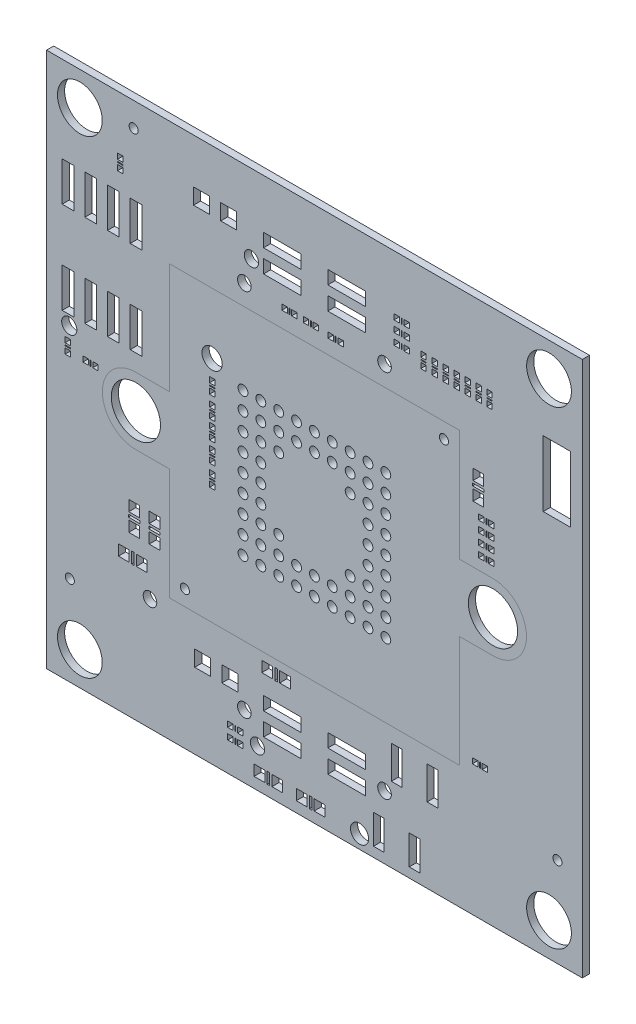
SolidWorks part; units mm, degrees
ref_plane "Front Plane" through (0, 0, 0) normal (0, 0, 1) x (1, 0, 0)
ref_plane "Top Plane" through (0, 0, 0) normal (0, 1, 0) x (1, 0, 0)
ref_plane "Right Plane" through (0, 0, 0) normal (1, 0, 0) x (0, 0, -1)
sketch "Model" plane through (0, 0, 0) normal (0, 0, 1) x (1, 0, 0)
  line L0 (482.6873, 104.7955) -> (482.6873, 151.0459)
  line L1 (482.6873, 151.0459) -> (497.6848, 151.0459)
  line L2 (497.6848, 151.0459) -> (497.6848, 104.7955)
  line L3 (497.6848, 104.7955) -> (482.6873, 104.7955)
  line L4 (532.6873, 104.7955) -> (532.6873, 151.0459)
  line L5 (532.6873, 151.0459) -> (547.6848, 151.0459)
  line L6 (547.6848, 151.0459) -> (547.6848, 104.7955)
  line L7 (547.6848, 104.7955) -> (532.6873, 104.7955)
  line L8 (457.6873, 13.5452) -> (457.6873, 54.7955)
  line L9 (457.6873, 54.7955) -> (472.6848, 54.7955)
  line L10 (472.6848, 54.7955) -> (472.6848, 13.5452)
  line L11 (472.6848, 13.5452) -> (457.6873, 13.5452)
  line L12 (507.6873, 13.5452) -> (507.6873, 54.7955)
  line L13 (507.6873, 54.7955) -> (522.6848, 54.7955)
  line L14 (522.6848, 54.7955) -> (522.6848, 13.5452)
  line L15 (522.6848, 13.5452) -> (507.6873, 13.5452)
  line L16 (356.2506, 69.0119) -> (303.7506, 69.0119)
  line L17 (303.7506, 69.0119) -> (303.7506, 87.7623)
  line L18 (303.7506, 87.7623) -> (356.2506, 87.7623)
  line L19 (356.2506, 87.7623) -> (356.2506, 69.0119)
  line L20 (356.2506, 100.762) -> (303.7506, 100.762)
  line L21 (303.7506, 100.762) -> (303.7506, 119.5123)
  line L22 (303.7506, 119.5123) -> (356.2506, 119.5123)
  line L23 (356.2506, 119.5123) -> (356.2506, 100.762)
  line L24 (446.2506, 69.0119) -> (393.7506, 69.0119)
  line L25 (393.7506, 69.0119) -> (393.7506, 87.7623)
  line L26 (393.7506, 87.7623) -> (446.2506, 87.7623)
  line L27 (446.2506, 87.7623) -> (446.2506, 69.0119)
  line L28 (446.2506, 100.762) -> (393.7506, 100.762)
  line L29 (393.7506, 100.762) -> (393.7506, 119.5123)
  line L30 (393.7506, 119.5123) -> (446.2506, 119.5123)
  line L31 (446.2506, 119.5123) -> (446.2506, 100.762)
  line L32 (356.2506, 630.4877) -> (303.7506, 630.4877)
  line L33 (303.7506, 630.4877) -> (303.7506, 649.238)
  line L34 (303.7506, 649.238) -> (356.2506, 649.238)
  line L35 (356.2506, 649.238) -> (356.2506, 630.4877)
  line L36 (356.2506, 662.2377) -> (303.7506, 662.2377)
  line L37 (303.7506, 662.2377) -> (303.7506, 680.9881)
  line L38 (303.7506, 680.9881) -> (356.2506, 680.9881)
  line L39 (356.2506, 680.9881) -> (356.2506, 662.2377)
  line L40 (446.2506, 630.4877) -> (393.7506, 630.4877)
  line L41 (393.7506, 630.4877) -> (393.7506, 649.238)
  line L42 (393.7506, 649.238) -> (446.2506, 649.238)
  line L43 (446.2506, 649.238) -> (446.2506, 630.4877)
  line L44 (446.2506, 662.2377) -> (393.7506, 662.2377)
  line L45 (393.7506, 662.2377) -> (393.7506, 680.9881)
  line L46 (393.7506, 680.9881) -> (446.2506, 680.9881)
  line L47 (446.2506, 680.9881) -> (446.2506, 662.2377)
  line L48 (603.6868, 190.2972) -> (603.6868, 182.6772)
  line L49 (603.6868, 182.6772) -> (596.0668, 182.6772)
  line L50 (596.0668, 182.6772) -> (596.0668, 190.2972)
  line L51 (596.0668, 190.2972) -> (603.6868, 190.2972)
  line L52 (617.5222, 190.2972) -> (617.5222, 182.6772)
  line L53 (617.5222, 182.6772) -> (609.9022, 182.6772)
  line L54 (609.9022, 182.6772) -> (609.9022, 190.2972)
  line L55 (609.9022, 190.2972) -> (617.5222, 190.2972)
  line L56 (607.4295, 190.2394) -> (606.1595, 190.2394)
  line L57 (606.1595, 190.2394) -> (606.1595, 182.7349)
  line L58 (606.1595, 182.7349) -> (607.4295, 182.7349)
  line L59 (607.4295, 182.7349) -> (607.4295, 190.2394)
  line L60 (267.3, 55.7214) -> (267.3, 63.3414)
  line L61 (267.3, 63.3414) -> (274.92, 63.3414)
  line L62 (274.92, 63.3414) -> (274.92, 55.7214)
  line L63 (274.92, 55.7214) -> (267.3, 55.7214)
  line L64 (253.4646, 55.7214) -> (253.4646, 63.3414)
  line L65 (253.4646, 63.3414) -> (261.0846, 63.3414)
  line L66 (261.0846, 63.3414) -> (261.0846, 55.7214)
  line L67 (261.0846, 55.7214) -> (253.4646, 55.7214)
  line L68 (263.5573, 55.7791) -> (264.8273, 55.7791)
  line L69 (264.8273, 55.7791) -> (264.8273, 63.2836)
  line L70 (264.8273, 63.2836) -> (263.5573, 63.2836)
  line L71 (263.5573, 63.2836) -> (263.5573, 55.7791)
  line L72 (267.4079, 40.3988) -> (267.4079, 48.0188)
  line L73 (267.4079, 48.0188) -> (275.028, 48.0188)
  line L74 (275.028, 48.0188) -> (275.028, 40.3988)
  line L75 (275.028, 40.3988) -> (267.4079, 40.3988)
  line L76 (253.5725, 40.3988) -> (253.5725, 48.0188)
  line L77 (253.5725, 48.0188) -> (261.1925, 48.0188)
  line L78 (261.1925, 48.0188) -> (261.1925, 40.3988)
  line L79 (261.1925, 40.3988) -> (253.5725, 40.3988)
  line L80 (263.6652, 40.4566) -> (264.9352, 40.4566)
  line L81 (264.9352, 40.4566) -> (264.9352, 47.961)
  line L82 (264.9352, 47.961) -> (263.6652, 47.961)
  line L83 (263.6652, 47.961) -> (263.6652, 40.4566)
  line L84 (623.8887, 639.6965) -> (616.2687, 639.6965)
  line L85 (616.2687, 639.6965) -> (616.2687, 647.3165)
  line L86 (616.2687, 647.3165) -> (623.8887, 647.3165)
  line L87 (623.8887, 647.3165) -> (623.8887, 639.6965)
  line L88 (623.8887, 625.8611) -> (616.2687, 625.8611)
  line L89 (616.2687, 625.8611) -> (616.2687, 633.4811)
  line L90 (616.2687, 633.4811) -> (623.8887, 633.4811)
  line L91 (623.8887, 633.4811) -> (623.8887, 625.8611)
  line L92 (623.831, 635.9538) -> (623.831, 637.2238)
  line L93 (623.831, 637.2238) -> (616.3265, 637.2238)
  line L94 (616.3265, 637.2238) -> (616.3265, 635.9538)
  line L95 (616.3265, 635.9538) -> (623.831, 635.9538)
  line L96 (601.0287, 633.4811) -> (608.6487, 633.4811)
  line L97 (608.6487, 633.4811) -> (608.6487, 625.8611)
  line L98 (608.6487, 625.8611) -> (601.0287, 625.8611)
  line L99 (601.0287, 625.8611) -> (601.0287, 633.4811)
  line L100 (601.0287, 647.3165) -> (608.6487, 647.3165)
  line L101 (608.6487, 647.3165) -> (608.6487, 639.6965)
  line L102 (608.6487, 639.6965) -> (601.0287, 639.6965)
  line L103 (601.0287, 639.6965) -> (601.0287, 647.3165)
  line L104 (601.0865, 637.2238) -> (601.0865, 635.9538)
  line L105 (601.0865, 635.9538) -> (608.5909, 635.9538)
  line L106 (608.5909, 635.9538) -> (608.5909, 637.2238)
  line L107 (608.5909, 637.2238) -> (601.0865, 637.2238)
  line L108 (618.7414, 467.3609) -> (618.7414, 474.9809)
  line L109 (618.7414, 474.9809) -> (626.3615, 474.9809)
  line L110 (626.3615, 474.9809) -> (626.3615, 467.3609)
  line L111 (626.3615, 467.3609) -> (618.7414, 467.3609)
  line L112 (604.906, 467.3609) -> (604.906, 474.9809)
  line L113 (604.906, 474.9809) -> (612.526, 474.9809)
  line L114 (612.526, 474.9809) -> (612.526, 467.3609)
  line L115 (612.526, 467.3609) -> (604.906, 467.3609)
  line L116 (614.9987, 467.4187) -> (616.2687, 467.4187)
  line L117 (616.2687, 467.4187) -> (616.2687, 474.9232)
  line L118 (616.2687, 474.9232) -> (614.9987, 474.9232)
  line L119 (614.9987, 474.9232) -> (614.9987, 467.4187)
  line L120 (612.526, 459.7409) -> (612.526, 452.1209)
  line L121 (612.526, 452.1209) -> (604.906, 452.1209)
  line L122 (604.906, 452.1209) -> (604.906, 459.7409)
  line L123 (604.906, 459.7409) -> (612.526, 459.7409)
  line L124 (626.3615, 459.7409) -> (626.3615, 452.1209)
  line L125 (626.3615, 452.1209) -> (618.7414, 452.1209)
  line L126 (618.7414, 452.1209) -> (618.7414, 459.7409)
  line L127 (618.7414, 459.7409) -> (626.3615, 459.7409)
  line L128 (616.2687, 459.6831) -> (614.9987, 459.6831)
  line L129 (614.9987, 459.6831) -> (614.9987, 452.1787)
  line L130 (614.9987, 452.1787) -> (616.2687, 452.1787)
  line L131 (616.2687, 452.1787) -> (616.2687, 459.6831)
  line L132 (106.9977, 667.319) -> (99.3777, 667.319)
  line L133 (99.3777, 667.319) -> (99.3777, 674.939)
  line L134 (99.3777, 674.939) -> (106.9977, 674.939)
  line L135 (106.9977, 674.939) -> (106.9977, 667.319)
  line L136 (106.9977, 653.4836) -> (99.3777, 653.4836)
  line L137 (99.3777, 653.4836) -> (99.3777, 661.1036)
  line L138 (99.3777, 661.1036) -> (106.9977, 661.1036)
  line L139 (106.9977, 661.1036) -> (106.9977, 653.4836)
  line L140 (106.9399, 663.5763) -> (106.9399, 664.8463)
  line L141 (106.9399, 664.8463) -> (99.4355, 664.8463)
  line L142 (99.4355, 664.8463) -> (99.4355, 663.5763)
  line L143 (99.4355, 663.5763) -> (106.9399, 663.5763)
  line L144 (64.7028, 397.1933) -> (64.7028, 404.8133)
  line L145 (64.7028, 404.8133) -> (72.3228, 404.8133)
  line L146 (72.3228, 404.8133) -> (72.3228, 397.1933)
  line L147 (72.3228, 397.1933) -> (64.7028, 397.1933)
  line L148 (50.8674, 397.1933) -> (50.8674, 404.8133)
  line L149 (50.8674, 404.8133) -> (58.4874, 404.8133)
  line L150 (58.4874, 404.8133) -> (58.4874, 397.1933)
  line L151 (58.4874, 397.1933) -> (50.8674, 397.1933)
  line L152 (60.9601, 397.2511) -> (62.2301, 397.2511)
  line L153 (62.2301, 397.2511) -> (62.2301, 404.7555)
  line L154 (62.2301, 404.7555) -> (60.9601, 404.7555)
  line L155 (60.9601, 404.7555) -> (60.9601, 397.2511)
  line L156 (26.0351, 402.0231) -> (33.6551, 402.0231)
  line L157 (33.6551, 402.0231) -> (33.6551, 394.4031)
  line L158 (33.6551, 394.4031) -> (26.0351, 394.4031)
  line L159 (26.0351, 394.4031) -> (26.0351, 402.0231)
  line L160 (26.0351, 415.8585) -> (33.6551, 415.8585)
  line L161 (33.6551, 415.8585) -> (33.6551, 408.2385)
  line L162 (33.6551, 408.2385) -> (26.0351, 408.2385)
  line L163 (26.0351, 408.2385) -> (26.0351, 415.8585)
  line L164 (26.0928, 405.7658) -> (26.0928, 404.4958)
  line L165 (26.0928, 404.4958) -> (33.5973, 404.4958)
  line L166 (33.5973, 404.4958) -> (33.5973, 405.7658)
  line L167 (33.5973, 405.7658) -> (26.0928, 405.7658)
  line L168 (562.6111, 639.6965) -> (554.9911, 639.6965)
  line L169 (554.9911, 639.6965) -> (554.9911, 647.3165)
  line L170 (554.9911, 647.3165) -> (562.6111, 647.3165)
  line L171 (562.6111, 647.3165) -> (562.6111, 639.6965)
  line L172 (562.6111, 625.8611) -> (554.9911, 625.8611)
  line L173 (554.9911, 625.8611) -> (554.9911, 633.4811)
  line L174 (554.9911, 633.4811) -> (562.6111, 633.4811)
  line L175 (562.6111, 633.4811) -> (562.6111, 625.8611)
  line L176 (562.5534, 635.9538) -> (562.5534, 637.2238)
  line L177 (562.5534, 637.2238) -> (555.0489, 637.2238)
  line L178 (555.0489, 637.2238) -> (555.0489, 635.9538)
  line L179 (555.0489, 635.9538) -> (562.5534, 635.9538)
  line L180 (539.4336, 633.4811) -> (547.0536, 633.4811)
  line L181 (547.0536, 633.4811) -> (547.0536, 625.8611)
  line L182 (547.0536, 625.8611) -> (539.4336, 625.8611)
  line L183 (539.4336, 625.8611) -> (539.4336, 633.4811)
  line L184 (539.4336, 647.3165) -> (547.0536, 647.3165)
  line L185 (547.0536, 647.3165) -> (547.0536, 639.6965)
  line L186 (547.0536, 639.6965) -> (539.4336, 639.6965)
  line L187 (539.4336, 639.6965) -> (539.4336, 647.3165)
  line L188 (539.4914, 637.2238) -> (539.4914, 635.9538)
  line L189 (539.4914, 635.9538) -> (546.9958, 635.9538)
  line L190 (546.9958, 635.9538) -> (546.9958, 637.2238)
  line L191 (546.9958, 637.2238) -> (539.4914, 637.2238)
  line L192 (500.381, 635.3188) -> (500.381, 642.9388)
  line L193 (500.381, 642.9388) -> (508.001, 642.9388)
  line L194 (508.001, 642.9388) -> (508.001, 635.3188)
  line L195 (508.001, 635.3188) -> (500.381, 635.3188)
  line L196 (486.5456, 635.3188) -> (486.5456, 642.9388)
  line L197 (486.5456, 642.9388) -> (494.1656, 642.9388)
  line L198 (494.1656, 642.9388) -> (494.1656, 635.3188)
  line L199 (494.1656, 635.3188) -> (486.5456, 635.3188)
  line L200 (496.6383, 635.3765) -> (497.9083, 635.3765)
  line L201 (497.9083, 635.3765) -> (497.9083, 642.881)
  line L202 (497.9083, 642.881) -> (496.6383, 642.881)
  line L203 (496.6383, 642.881) -> (496.6383, 635.3765)
  line L204 (578.1687, 639.6965) -> (570.5486, 639.6965)
  line L205 (570.5486, 639.6965) -> (570.5486, 647.3165)
  line L206 (570.5486, 647.3165) -> (578.1687, 647.3165)
  line L207 (578.1687, 647.3165) -> (578.1687, 639.6965)
  line L208 (578.1687, 625.8611) -> (570.5486, 625.8611)
  line L209 (570.5486, 625.8611) -> (570.5486, 633.4811)
  line L210 (570.5486, 633.4811) -> (578.1687, 633.4811)
  line L211 (578.1687, 633.4811) -> (578.1687, 625.8611)
  line L212 (578.1109, 635.9538) -> (578.1109, 637.2238)
  line L213 (578.1109, 637.2238) -> (570.6064, 637.2238)
  line L214 (570.6064, 637.2238) -> (570.6064, 635.9538)
  line L215 (570.6064, 635.9538) -> (578.1109, 635.9538)
  line L216 (585.7887, 633.4811) -> (593.4087, 633.4811)
  line L217 (593.4087, 633.4811) -> (593.4087, 625.8611)
  line L218 (593.4087, 625.8611) -> (585.7887, 625.8611)
  line L219 (585.7887, 625.8611) -> (585.7887, 633.4811)
  line L220 (585.7887, 647.3165) -> (593.4087, 647.3165)
  line L221 (593.4087, 647.3165) -> (593.4087, 639.6965)
  line L222 (593.4087, 639.6965) -> (585.7887, 639.6965)
  line L223 (585.7887, 639.6965) -> (585.7887, 647.3165)
  line L224 (585.8464, 637.2238) -> (585.8464, 635.9538)
  line L225 (585.8464, 635.9538) -> (593.3509, 635.9538)
  line L226 (593.3509, 635.9538) -> (593.3509, 637.2238)
  line L227 (593.3509, 637.2238) -> (585.8464, 637.2238)
  line L228 (523.876, 633.4811) -> (531.4961, 633.4811)
  line L229 (531.4961, 633.4811) -> (531.4961, 625.8611)
  line L230 (531.4961, 625.8611) -> (523.876, 625.8611)
  line L231 (523.876, 625.8611) -> (523.876, 633.4811)
  line L232 (523.876, 647.3165) -> (531.4961, 647.3165)
  line L233 (531.4961, 647.3165) -> (531.4961, 639.6965)
  line L234 (531.4961, 639.6965) -> (523.876, 639.6965)
  line L235 (523.876, 639.6965) -> (523.876, 647.3165)
  line L236 (523.9338, 637.2238) -> (523.9338, 635.9538)
  line L237 (523.9338, 635.9538) -> (531.4383, 635.9538)
  line L238 (531.4383, 635.9538) -> (531.4383, 637.2238)
  line L239 (531.4383, 637.2238) -> (523.9338, 637.2238)
  line L240 (612.526, 444.5009) -> (612.526, 436.8809)
  line L241 (612.526, 436.8809) -> (604.906, 436.8809)
  line L242 (604.906, 436.8809) -> (604.906, 444.5009)
  line L243 (604.906, 444.5009) -> (612.526, 444.5009)
  line L244 (626.3615, 444.5009) -> (626.3615, 436.8809)
  line L245 (626.3615, 436.8809) -> (618.7414, 436.8809)
  line L246 (618.7414, 436.8809) -> (618.7414, 444.5009)
  line L247 (618.7414, 444.5009) -> (626.3615, 444.5009)
  line L248 (616.2687, 444.4431) -> (614.9987, 444.4431)
  line L249 (614.9987, 444.4431) -> (614.9987, 436.9386)
  line L250 (614.9987, 436.9386) -> (616.2687, 436.9386)
  line L251 (616.2687, 436.9386) -> (616.2687, 444.4431)
  line L252 (500.3137, 666.1163) -> (500.3137, 673.7363)
  line L253 (500.3137, 673.7363) -> (507.9337, 673.7363)
  line L254 (507.9337, 673.7363) -> (507.9337, 666.1163)
  line L255 (507.9337, 666.1163) -> (500.3137, 666.1163)
  line L256 (486.4783, 666.1163) -> (486.4783, 673.7363)
  line L257 (486.4783, 673.7363) -> (494.0983, 673.7363)
  line L258 (494.0983, 673.7363) -> (494.0983, 666.1163)
  line L259 (494.0983, 666.1163) -> (486.4783, 666.1163)
  line L260 (496.571, 666.1741) -> (497.841, 666.1741)
  line L261 (497.841, 666.1741) -> (497.841, 673.6786)
  line L262 (497.841, 673.6786) -> (496.571, 673.6786)
  line L263 (496.571, 673.6786) -> (496.571, 666.1741)
  line L264 (500.381, 650.8763) -> (500.381, 658.4963)
  line L265 (500.381, 658.4963) -> (508.001, 658.4963)
  line L266 (508.001, 658.4963) -> (508.001, 650.8763)
  line L267 (508.001, 650.8763) -> (500.381, 650.8763)
  line L268 (486.5456, 650.8763) -> (486.5456, 658.4963)
  line L269 (486.5456, 658.4963) -> (494.1656, 658.4963)
  line L270 (494.1656, 658.4963) -> (494.1656, 650.8763)
  line L271 (494.1656, 650.8763) -> (486.5456, 650.8763)
  line L272 (496.6383, 650.9341) -> (497.9083, 650.9341)
  line L273 (497.9083, 650.9341) -> (497.9083, 658.4385)
  line L274 (497.9083, 658.4385) -> (496.6383, 658.4385)
  line L275 (496.6383, 658.4385) -> (496.6383, 650.9341)
  line L276 (337.0028, 607.0231) -> (337.0028, 599.4031)
  line L277 (337.0028, 599.4031) -> (329.3828, 599.4031)
  line L278 (329.3828, 599.4031) -> (329.3828, 607.0231)
  line L279 (329.3828, 607.0231) -> (337.0028, 607.0231)
  line L280 (350.8382, 607.0231) -> (350.8382, 599.4031)
  line L281 (350.8382, 599.4031) -> (343.2182, 599.4031)
  line L282 (343.2182, 599.4031) -> (343.2182, 607.0231)
  line L283 (343.2182, 607.0231) -> (350.8382, 607.0231)
  line L284 (340.7455, 606.9653) -> (339.4755, 606.9653)
  line L285 (339.4755, 606.9653) -> (339.4755, 599.4609)
  line L286 (339.4755, 599.4609) -> (340.7455, 599.4609)
  line L287 (340.7455, 599.4609) -> (340.7455, 606.9653)
  line L288 (373.2207, 599.4031) -> (373.2207, 607.0231)
  line L289 (373.2207, 607.0231) -> (380.8407, 607.0231)
  line L290 (380.8407, 607.0231) -> (380.8407, 599.4031)
  line L291 (380.8407, 599.4031) -> (373.2207, 599.4031)
  line L292 (359.3853, 599.4031) -> (359.3853, 607.0231)
  line L293 (359.3853, 607.0231) -> (367.0053, 607.0231)
  line L294 (367.0053, 607.0231) -> (367.0053, 599.4031)
  line L295 (367.0053, 599.4031) -> (359.3853, 599.4031)
  line L296 (369.478, 599.4609) -> (370.748, 599.4609)
  line L297 (370.748, 599.4609) -> (370.748, 606.9653)
  line L298 (370.748, 606.9653) -> (369.478, 606.9653)
  line L299 (369.478, 606.9653) -> (369.478, 599.4609)
  line L300 (407.7623, 597.6949) -> (407.7623, 605.315)
  line L301 (407.7623, 605.315) -> (415.3823, 605.315)
  line L302 (415.3823, 605.315) -> (415.3823, 597.6949)
  line L303 (415.3823, 597.6949) -> (407.7623, 597.6949)
  line L304 (393.9268, 597.6949) -> (393.9268, 605.315)
  line L305 (393.9268, 605.315) -> (401.5469, 605.315)
  line L306 (401.5469, 605.315) -> (401.5469, 597.6949)
  line L307 (401.5469, 597.6949) -> (393.9268, 597.6949)
  line L308 (404.0196, 597.7527) -> (405.2896, 597.7527)
  line L309 (405.2896, 597.7527) -> (405.2896, 605.2572)
  line L310 (405.2896, 605.2572) -> (404.0196, 605.2572)
  line L311 (404.0196, 605.2572) -> (404.0196, 597.7527)
  line L312 (618.7414, 482.601) -> (618.7414, 490.221)
  line L313 (618.7414, 490.221) -> (626.3615, 490.221)
  line L314 (626.3615, 490.221) -> (626.3615, 482.601)
  line L315 (626.3615, 482.601) -> (618.7414, 482.601)
  line L316 (604.906, 482.601) -> (604.906, 490.221)
  line L317 (604.906, 490.221) -> (612.526, 490.221)
  line L318 (612.526, 490.221) -> (612.526, 482.601)
  line L319 (612.526, 482.601) -> (604.906, 482.601)
  line L320 (614.9987, 482.6587) -> (616.2687, 482.6587)
  line L321 (616.2687, 482.6587) -> (616.2687, 490.1632)
  line L322 (616.2687, 490.1632) -> (614.9987, 490.1632)
  line L323 (614.9987, 490.1632) -> (614.9987, 482.6587)
  line L324 (235.7779, 405.2032) -> (228.1579, 405.2032)
  line L325 (228.1579, 405.2032) -> (228.1579, 412.8232)
  line L326 (228.1579, 412.8232) -> (235.7779, 412.8232)
  line L327 (235.7779, 412.8232) -> (235.7779, 405.2032)
  line L328 (235.7779, 391.3678) -> (228.1579, 391.3678)
  line L329 (228.1579, 391.3678) -> (228.1579, 398.9878)
  line L330 (228.1579, 398.9878) -> (235.7779, 398.9878)
  line L331 (235.7779, 398.9878) -> (235.7779, 391.3678)
  line L332 (235.7201, 401.4605) -> (235.7201, 402.7305)
  line L333 (235.7201, 402.7305) -> (228.2157, 402.7305)
  line L334 (228.2157, 402.7305) -> (228.2157, 401.4605)
  line L335 (228.2157, 401.4605) -> (235.7201, 401.4605)
  line L336 (235.7779, 377.2505) -> (228.1579, 377.2505)
  line L337 (228.1579, 377.2505) -> (228.1579, 384.8705)
  line L338 (228.1579, 384.8705) -> (235.7779, 384.8705)
  line L339 (235.7779, 384.8705) -> (235.7779, 377.2505)
  line L340 (235.7779, 363.415) -> (228.1579, 363.415)
  line L341 (228.1579, 363.415) -> (228.1579, 371.035)
  line L342 (228.1579, 371.035) -> (235.7779, 371.035)
  line L343 (235.7779, 371.035) -> (235.7779, 363.415)
  line L344 (235.7201, 373.5077) -> (235.7201, 374.7777)
  line L345 (235.7201, 374.7777) -> (228.2157, 374.7777)
  line L346 (228.2157, 374.7777) -> (228.2157, 373.5077)
  line L347 (228.2157, 373.5077) -> (235.7201, 373.5077)
  line L348 (228.1579, 425.0311) -> (235.7779, 425.0311)
  line L349 (235.7779, 425.0311) -> (235.7779, 417.4111)
  line L350 (235.7779, 417.4111) -> (228.1579, 417.4111)
  line L351 (228.1579, 417.4111) -> (228.1579, 425.0311)
  line L352 (228.1579, 438.8665) -> (235.7779, 438.8665)
  line L353 (235.7779, 438.8665) -> (235.7779, 431.2465)
  line L354 (235.7779, 431.2465) -> (228.1579, 431.2465)
  line L355 (228.1579, 431.2465) -> (228.1579, 438.8665)
  line L356 (228.2157, 428.7738) -> (228.2157, 427.5038)
  line L357 (228.2157, 427.5038) -> (235.7201, 427.5038)
  line L358 (235.7201, 427.5038) -> (235.7201, 428.7738)
  line L359 (235.7201, 428.7738) -> (228.2157, 428.7738)
  line L360 (228.1579, 341.7234) -> (235.7779, 341.7234)
  line L361 (235.7779, 341.7234) -> (235.7779, 334.1034)
  line L362 (235.7779, 334.1034) -> (228.1579, 334.1034)
  line L363 (228.1579, 334.1034) -> (228.1579, 341.7234)
  line L364 (228.1579, 355.5588) -> (235.7779, 355.5588)
  line L365 (235.7779, 355.5588) -> (235.7779, 347.9388)
  line L366 (235.7779, 347.9388) -> (228.1579, 347.9388)
  line L367 (228.1579, 347.9388) -> (228.1579, 355.5588)
  line L368 (228.2157, 345.4661) -> (228.2157, 344.1961)
  line L369 (228.2157, 344.1961) -> (235.7201, 344.1961)
  line L370 (235.7201, 344.1961) -> (235.7201, 345.4661)
  line L371 (235.7201, 345.4661) -> (228.2157, 345.4661)
  line L372 (235.7779, 460.7144) -> (228.1579, 460.7144)
  line L373 (228.1579, 460.7144) -> (228.1579, 468.3344)
  line L374 (228.1579, 468.3344) -> (235.7779, 468.3344)
  line L375 (235.7779, 468.3344) -> (235.7779, 460.7144)
  line L376 (235.7779, 446.879) -> (228.1579, 446.879)
  line L377 (228.1579, 446.879) -> (228.1579, 454.499)
  line L378 (228.1579, 454.499) -> (235.7779, 454.499)
  line L379 (235.7779, 454.499) -> (235.7779, 446.879)
  line L380 (235.7201, 456.9717) -> (235.7201, 458.2417)
  line L381 (235.7201, 458.2417) -> (228.2157, 458.2417)
  line L382 (228.2157, 458.2417) -> (228.2157, 456.9717)
  line L383 (228.2157, 456.9717) -> (235.7201, 456.9717)
  line L384 (612.0199, 526.6574) -> (597.0225, 526.6574)
  line L385 (597.0225, 526.6574) -> (597.0225, 541.6548)
  line L386 (597.0225, 541.6548) -> (612.0199, 541.6548)
  line L387 (612.0199, 541.6548) -> (612.0199, 526.6574)
  line L388 (612.0199, 501.6523) -> (597.0225, 501.6523)
  line L389 (597.0225, 501.6523) -> (597.0225, 516.6497)
  line L390 (597.0225, 516.6497) -> (612.0199, 516.6497)
  line L391 (612.0199, 516.6497) -> (612.0199, 501.6523)
  line L392 (612.521, 519.9009) -> (612.521, 523.4061)
  line L393 (612.521, 523.4061) -> (596.5215, 523.4061)
  line L394 (596.5215, 523.4061) -> (596.5215, 519.9009)
  line L395 (596.5215, 519.9009) -> (612.521, 519.9009)
  line L396 (158.629, 247.8918) -> (143.6316, 247.8918)
  line L397 (143.6316, 247.8918) -> (143.6316, 262.8893)
  line L398 (143.6316, 262.8893) -> (158.629, 262.8893)
  line L399 (158.629, 262.8893) -> (158.629, 247.8918)
  line L400 (158.629, 222.8867) -> (143.6316, 222.8867)
  line L401 (143.6316, 222.8867) -> (143.6316, 237.8842)
  line L402 (143.6316, 237.8842) -> (158.629, 237.8842)
  line L403 (158.629, 237.8842) -> (158.629, 222.8867)
  line L404 (159.13, 241.1354) -> (159.13, 244.6406)
  line L405 (159.13, 244.6406) -> (143.1306, 244.6406)
  line L406 (143.1306, 244.6406) -> (143.1306, 241.1354)
  line L407 (143.1306, 241.1354) -> (159.13, 241.1354)
  line L408 (316.3068, 160.8515) -> (316.3068, 145.8541)
  line L409 (316.3068, 145.8541) -> (301.3094, 145.8541)
  line L410 (301.3094, 145.8541) -> (301.3094, 160.8515)
  line L411 (301.3094, 160.8515) -> (316.3068, 160.8515)
  line L412 (341.3119, 160.8515) -> (341.3119, 145.8541)
  line L413 (341.3119, 145.8541) -> (326.3145, 145.8541)
  line L414 (326.3145, 145.8541) -> (326.3145, 160.8515)
  line L415 (326.3145, 160.8515) -> (341.3119, 160.8515)
  line L416 (323.0632, 161.3525) -> (319.558, 161.3525)
  line L417 (319.558, 161.3525) -> (319.558, 145.3531)
  line L418 (319.558, 145.3531) -> (323.0632, 145.3531)
  line L419 (323.0632, 145.3531) -> (323.0632, 161.3525)
  line L420 (266.0655, 687.0714) -> (266.0655, 664.8463)
  line L421 (266.0655, 664.8463) -> (243.8405, 664.8463)
  line L422 (243.8405, 664.8463) -> (243.8405, 687.0714)
  line L423 (243.8405, 687.0714) -> (266.0655, 687.0714)
  line L424 (227.9655, 687.0714) -> (227.9655, 664.8463)
  line L425 (227.9655, 664.8463) -> (205.7404, 664.8463)
  line L426 (205.7404, 664.8463) -> (205.7404, 687.0714)
  line L427 (205.7404, 687.0714) -> (227.9655, 687.0714)
  line L428 (267.653, 127.6353) -> (267.653, 105.4102)
  line L429 (267.653, 105.4102) -> (245.428, 105.4102)
  line L430 (245.428, 105.4102) -> (245.428, 127.6353)
  line L431 (245.428, 127.6353) -> (267.653, 127.6353)
  line L432 (229.553, 127.6353) -> (229.553, 105.4102)
  line L433 (229.553, 105.4102) -> (207.3279, 105.4102)
  line L434 (207.3279, 105.4102) -> (207.3279, 127.6353)
  line L435 (207.3279, 127.6353) -> (229.553, 127.6353)
  line L445 (315.5194, 14.7263) -> (315.5194, 29.7238)
  line L446 (315.5194, 29.7238) -> (330.5169, 29.7238)
  line L447 (330.5169, 29.7238) -> (330.5169, 14.7263)
  line L448 (330.5169, 14.7263) -> (315.5194, 14.7263)
  line L449 (290.5144, 14.7263) -> (290.5144, 29.7238)
  line L450 (290.5144, 29.7238) -> (305.5118, 29.7238)
  line L451 (305.5118, 29.7238) -> (305.5118, 14.7263)
  line L452 (305.5118, 14.7263) -> (290.5144, 14.7263)
  line L453 (308.763, 14.2253) -> (312.2682, 14.2253)
  line L454 (312.2682, 14.2253) -> (312.2682, 30.2248)
  line L455 (312.2682, 30.2248) -> (308.763, 30.2248)
  line L456 (308.763, 30.2248) -> (308.763, 14.2253)
  line L457 (364.5669, 29.7238) -> (364.5669, 14.7263)
  line L458 (364.5669, 14.7263) -> (349.5695, 14.7263)
  line L459 (349.5695, 14.7263) -> (349.5695, 29.7238)
  line L460 (349.5695, 29.7238) -> (364.5669, 29.7238)
  line L461 (389.572, 29.7238) -> (389.572, 14.7263)
  line L462 (389.572, 14.7263) -> (374.5745, 14.7263)
  line L463 (374.5745, 14.7263) -> (374.5745, 29.7238)
  line L464 (374.5745, 29.7238) -> (389.572, 29.7238)
  line L465 (371.3233, 30.2248) -> (367.8181, 30.2248)
  line L466 (367.8181, 30.2248) -> (367.8181, 14.2253)
  line L467 (367.8181, 14.2253) -> (371.3233, 14.2253)
  line L468 (371.3233, 14.2253) -> (371.3233, 30.2248)
  line L469 (115.0565, 237.8842) -> (130.054, 237.8842)
  line L470 (130.054, 237.8842) -> (130.054, 222.8867)
  line L471 (130.054, 222.8867) -> (115.0565, 222.8867)
  line L472 (115.0565, 222.8867) -> (115.0565, 237.8842)
  line L473 (115.0565, 262.8893) -> (130.054, 262.8893)
  line L474 (130.054, 262.8893) -> (130.054, 247.8918)
  line L475 (130.054, 247.8918) -> (115.0565, 247.8918)
  line L476 (115.0565, 247.8918) -> (115.0565, 262.8893)
  line L477 (114.5555, 244.6406) -> (114.5555, 241.1354)
  line L478 (114.5555, 241.1354) -> (130.555, 241.1354)
  line L479 (130.555, 241.1354) -> (130.555, 244.6406)
  line L480 (130.555, 244.6406) -> (114.5555, 244.6406)
  line L481 (115.6464, 201.8091) -> (115.6464, 186.8116)
  line L482 (115.6464, 186.8116) -> (100.649, 186.8116)
  line L483 (100.649, 186.8116) -> (100.649, 201.8091)
  line L484 (100.649, 201.8091) -> (115.6464, 201.8091)
  line L485 (140.6515, 201.8091) -> (140.6515, 186.8116)
  line L486 (140.6515, 186.8116) -> (125.6541, 186.8116)
  line L487 (125.6541, 186.8116) -> (125.6541, 201.8091)
  line L488 (125.6541, 201.8091) -> (140.6515, 201.8091)
  line L489 (122.4028, 202.3101) -> (118.8976, 202.3101)
  line L490 (118.8976, 202.3101) -> (118.8976, 186.3106)
  line L491 (118.8976, 186.3106) -> (122.4028, 186.3106)
  line L492 (122.4028, 186.3106) -> (122.4028, 202.3101)
  line L493 (38.0941, 574.151) -> (21.8437, 574.151)
  line L494 (21.8437, 574.151) -> (21.8437, 629.151)
  line L495 (21.8437, 629.151) -> (38.0941, 629.151)
  line L496 (38.0941, 629.151) -> (38.0941, 574.151)
  line L497 (69.8441, 574.151) -> (53.5938, 574.151)
  line L498 (53.5938, 574.151) -> (53.5938, 629.151)
  line L499 (53.5938, 629.151) -> (69.8441, 629.151)
  line L500 (69.8441, 629.151) -> (69.8441, 574.151)
  line L501 (101.5942, 574.151) -> (85.3438, 574.151)
  line L502 (85.3438, 574.151) -> (85.3438, 629.151)
  line L503 (85.3438, 629.151) -> (101.5942, 629.151)
  line L504 (101.5942, 629.151) -> (101.5942, 574.151)
  line L505 (133.3442, 574.151) -> (117.0939, 574.151)
  line L506 (117.0939, 574.151) -> (117.0939, 629.151)
  line L507 (117.0939, 629.151) -> (133.3442, 629.151)
  line L508 (133.3442, 629.151) -> (133.3442, 574.151)
  line L509 (133.3442, 445.3956) -> (117.0939, 445.3956)
  line L510 (117.0939, 445.3956) -> (117.0939, 500.3956)
  line L511 (117.0939, 500.3956) -> (133.3442, 500.3956)
  line L512 (133.3442, 500.3956) -> (133.3442, 445.3956)
  line L513 (101.5942, 445.3956) -> (85.3438, 445.3956)
  line L514 (85.3438, 445.3956) -> (85.3438, 500.3956)
  line L515 (85.3438, 500.3956) -> (101.5942, 500.3956)
  line L516 (101.5942, 500.3956) -> (101.5942, 445.3956)
  line L517 (69.8441, 445.3956) -> (53.5938, 445.3956)
  line L518 (53.5938, 445.3956) -> (53.5938, 500.3956)
  line L519 (53.5938, 500.3956) -> (69.8441, 500.3956)
  line L520 (69.8441, 500.3956) -> (69.8441, 445.3956)
  line L521 (38.0941, 445.3956) -> (21.8437, 445.3956)
  line L522 (21.8437, 445.3956) -> (21.8437, 500.3956)
  line L523 (21.8437, 500.3956) -> (38.0941, 500.3956)
  line L524 (38.0941, 500.3956) -> (38.0941, 445.3956)
  line L529 (695.3264, 538.2017) -> (733.4265, 538.2017)
  line L530 (733.4265, 538.2017) -> (733.4265, 630.2007)
  line L531 (733.4265, 630.2007) -> (695.3264, 630.2007)
  line L532 (695.3264, 630.2007) -> (695.3264, 538.2017)
  circle A0 centre (144.7803, 156.8453) radius 9.4999
  circle A1 centre (121.9139, 716.1671) radius 6.35
  circle A2 centre (715.2273, 125.489) radius 6.35
  circle A3 centre (32.5565, 125.489) radius 6.35
  circle A4 centre (193.6754, 193.6754) radius 6.35
  circle A5 centre (556.3246, 556.3246) radius 6.35
  circle A6 centre (124.9994, 375) radius 34.4752
  circle A7 centre (625.0006, 375) radius 34.4752
  circle A8 centre (473.1255, 606.0262) radius 9.5374
  circle A9 centre (276.8745, 606.0262) radius 9.5374
  circle A10 centre (473.1255, 88.5001) radius 9.5374
  circle A11 centre (276.8745, 88.5001) radius 9.5374
  circle A12 centre (275, 475) radius 6.8739
  circle A13 centre (300, 475) radius 6.8739
  circle A14 centre (325, 475) radius 6.8739
  circle A15 centre (350, 475) radius 6.8739
  circle A16 centre (375, 475) radius 6.8739
  circle A17 centre (400, 475) radius 6.8739
  circle A18 centre (425, 475) radius 6.8739
  circle A19 centre (450, 475) radius 6.8739
  circle A20 centre (475, 475) radius 6.8739
  circle A21 centre (275, 450) radius 6.8739
  circle A22 centre (300, 450) radius 6.8739
  circle A23 centre (325, 450) radius 6.8739
  circle A24 centre (350, 450) radius 6.8739
  circle A25 centre (375, 450) radius 6.8739
  circle A26 centre (400, 450) radius 6.8739
  circle A27 centre (425, 450) radius 6.8739
  circle A28 centre (450, 450) radius 6.8739
  circle A29 centre (475, 450) radius 6.8739
  circle A30 centre (275, 425) radius 6.8739
  circle A31 centre (300, 425) radius 6.8739
  circle A32 centre (325, 425) radius 6.8739
  circle A33 centre (425, 425) radius 6.8739
  circle A34 centre (450, 425) radius 6.8739
  circle A35 centre (475, 425) radius 6.8739
  circle A36 centre (275, 400) radius 6.8739
  circle A37 centre (300, 400) radius 6.8739
  circle A38 centre (450, 400) radius 6.8739
  circle A39 centre (475, 400) radius 6.8739
  circle A40 centre (275, 375) radius 6.8739
  circle A41 centre (300, 375) radius 6.8739
  circle A42 centre (450, 375) radius 6.8739
  circle A43 centre (475, 375) radius 6.8739
  circle A44 centre (275, 350) radius 6.8739
  circle A45 centre (300, 350) radius 6.8739
  circle A46 centre (450, 350) radius 6.8739
  circle A47 centre (475, 350) radius 6.8739
  circle A48 centre (275, 325) radius 6.8739
  circle A49 centre (300, 325) radius 6.8739
  circle A50 centre (325, 325) radius 6.8739
  circle A51 centre (425, 325) radius 6.8739
  circle A52 centre (450, 325) radius 6.8739
  circle A53 centre (475, 325) radius 6.8739
  circle A54 centre (275, 300) radius 6.8739
  circle A55 centre (300, 300) radius 6.8739
  circle A56 centre (325, 300) radius 6.8739
  circle A57 centre (350, 300) radius 6.8739
  circle A58 centre (375, 300) radius 6.8739
  circle A59 centre (400, 300) radius 6.8739
  circle A60 centre (425, 300) radius 6.8739
  circle A61 centre (450, 300) radius 6.8739
  circle A62 centre (475, 300) radius 6.8739
  circle A63 centre (275, 275) radius 6.8739
  circle A64 centre (300, 275) radius 6.8739
  circle A65 centre (325, 275) radius 6.8739
  circle A66 centre (350, 275) radius 6.8739
  circle A67 centre (375, 275) radius 6.8739
  circle A68 centre (400, 275) radius 6.8739
  circle A69 centre (425, 275) radius 6.8739
  circle A70 centre (450, 275) radius 6.8739
  circle A71 centre (475, 275) radius 6.8739
  circle A72 centre (703.41, 46.59) radius 31.35
  circle A73 centre (46.59, 46.59) radius 31.35
  circle A74 centre (703.41, 703.41) radius 31.35
  circle A75 centre (46.59, 703.41) radius 31.35
  circle A76 centre (438.1514, 19.0502) radius 12.7002
  circle A77 centre (295.2758, 53.9754) radius 9.9998
  circle A78 centre (286.7502, 640.3628) radius 9.9998
  circle A84 centre (31.7504, 431.8009) radius 10.6327
  circle A85 centre (231.7755, 492.126) radius 14.1999
ref_plane "Plane1" through (0, 0, 100) normal (0, 0, 1) x (1, 0, 0)
sketch "Sketch2" plane through (0, 0, 100) normal (0, 0, 1) x (1, 0, 0)
  line L4 (750, 750) -> (0, 750)
  line L5 (0, 750) -> (0, 0)
  line L6 (0, 0) -> (750, 0)
  line L7 (750, 0) -> (750, 750)
extrude "Boss-Extrude1" add sketch "Sketch2" along normal blind 10
ref_plane "Plane2" through (0, 0, 200) normal (0, 0, 1) x (1, 0, 0)
sketch "Sketch3" plane through (0, 0, 200) normal (0, 0, 1) x (1, 0, 0)
  line L10 (171.8745, 577.0003) -> (578.1255, 578.1255)
  line L11 (171.8745, 577.0003) -> (171.8745, 421.8752)
  line L12 (171.8745, 421.8752) -> (124.9994, 421.8752)
  line L13 (124.9994, 328.1248) -> (171.8745, 328.1248)
  line L14 (171.8745, 328.1248) -> (171.8745, 171.8745)
  line L15 (171.8745, 171.8745) -> (578.1255, 171.8745)
  line L16 (578.1255, 171.8745) -> (578.1255, 328.1248)
  line L17 (578.1255, 328.1248) -> (625.0006, 328.1248)
  line L18 (625.0006, 421.8752) -> (578.1255, 421.8752)
  line L19 (578.1255, 421.8752) -> (578.1255, 578.1255)
  arc A4 (124.9994, 421.8752) -> (78.1242, 375) centre (124.9993, 375) ccw
  arc A5 (78.1242, 375) -> (124.9994, 328.1248) centre (124.9993, 375) ccw
  arc A6 (625.0006, 328.1248) -> (671.8758, 375) centre (625.0007, 375) ccw
  arc A7 (671.8758, 375) -> (625.0006, 421.8752) centre (625.0007, 375) ccw
extrude "Cut-Extrude1" cut sketch "Model" along normal blind 377
split line "Split Line1"
